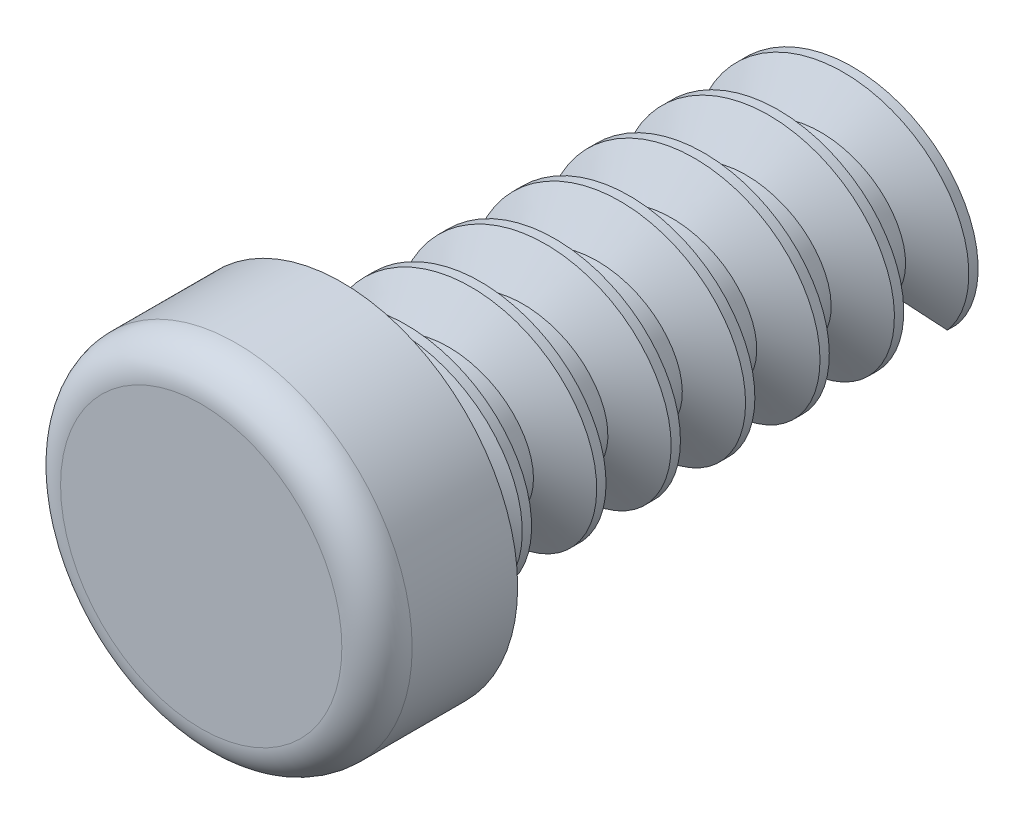
SolidWorks part; units mm, degrees
ref_plane "Front Plane" through (0, 0, 0) normal (0, 0, 1) x (1, 0, 0)
ref_plane "Top Plane" through (0, 0, 0) normal (0, 1, 0) x (1, 0, 0)
ref_plane "Right Plane" through (0, 0, 0) normal (1, 0, 0) x (0, 0, -1)
sketch "Sketch1" plane through (0, 0, 0) normal (0, 0, 1) x (1, 0, 0)
  circle A0 centre (0, 0) radius 2.25
  dimension "D1" = 4.5
extrude "Boss-Extrude1" add sketch "Sketch1" along normal blind 15
thread "Thread1" pitch 2.1167 method extrude profile "Thread Profile1" start angle 0, offset 0, length 14, pitch 2.1167, diameter 4.5
ref_plane "Plane1" through (-2.25, 0, 15) normal (0, -1, 0) x (-1, 0, 0)
sketch "Thread Profile1" plane through (-2.25, 0, 15) normal (0, -1, 0) x (-1, 0, 0)
  line L0 (0, 0) -> (0, 2.1167) construction
  line L1 (0, 0) -> (1.1457, 0.6615)
  line L2 (1.1457, 0.6615) -> (1.1457, 0.926)
  line L3 (1.1457, 0.926) -> (0, 1.5875)
  line L4 (1.1457, 0.7937) -> (0, 0.7937) construction
  line L11 (0, 0) -> (0, 1.5875)
  point P2 (0, 0)
  dimension "Pitch" = 2.1167
  dimension "Profile_Angle" = 60
  dimension "Profile_Land" = 0.2646
  dimension "Profile_Height" = 1.1457
sketch "Sketch4" plane through (0, 0, 15) normal (0, 0, 1) x (1, 0, 0)
  circle A0 centre (0, 0) radius 5
  dimension "D1" = 10
extrude "Boss-Extrude2" add sketch "Sketch4" along normal blind 4
fillet "Fillet1" radius 1 1 edges at (5, 0, 19)
